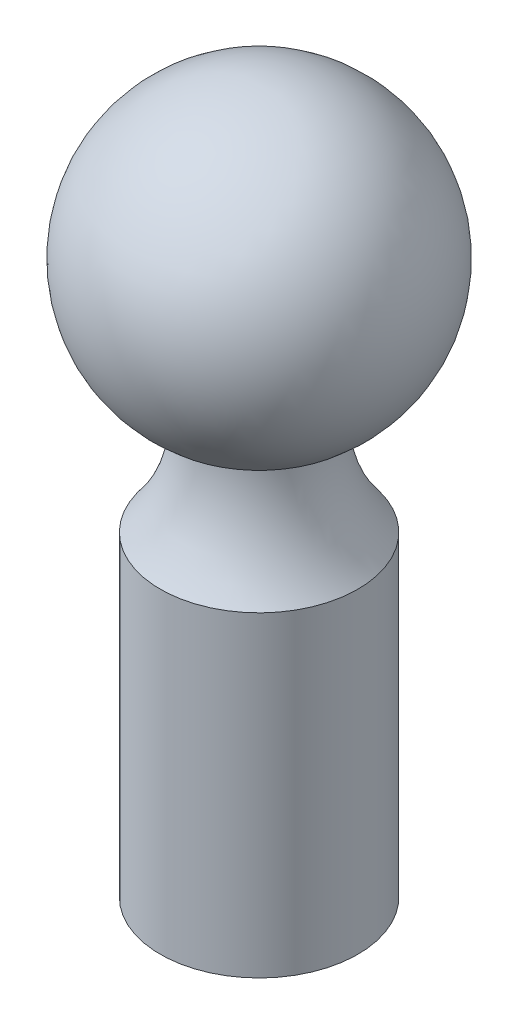
SolidWorks part; units mm, degrees
ref_plane "Front Plane" through (0, 0, 0) normal (0, 0, 1) x (1, 0, 0)
ref_plane "Top Plane" through (0, 0, 0) normal (0, 1, 0) x (1, 0, 0)
ref_plane "Right Plane" through (0, 0, 0) normal (1, 0, 0) x (0, 0, -1)
sketch "Sketch1" plane through (0, 0, 0) normal (0, 0, 1) x (1, 0, 0)
  line L0 (0, 0) -> (0, 9.5)
  line L1 (0, 0) -> (0, -9.5)
  arc A0 (0, -9.5) -> (0, 9.5) centre (0, 0) cw
  point P0 (0, 0)
  point P2 (0, 0)
  point P5 (0, 0)
  point P6 (0, 0)
  point P7 (-0.1852, 3.3377)
  dimension "D1" = 9.5
revolve "Revolve1" add sketch "Sketch1" angle 360 about L0
sketch "Sketch2" plane through (0, 0, 0) normal (0, 1, 0) x (1, 0, 0)
  circle A0 centre (0, 0) radius 4
  dimension "D1" = 8
extrude "Boss-Extrude1" add sketch "Sketch2" against normal blind 15
sketch "Sketch3" plane through (0, -15, 0) normal (0, -1, 0) x (1, 0, 0)
  circle A0 centre (0, 0) radius 6.25
  dimension "D1" = 12.5
extrude "Boss-Extrude2" add sketch "Sketch3" along normal blind 20
fillet "Fillet1" radius 10 1 edges at (0, -15, 4)
